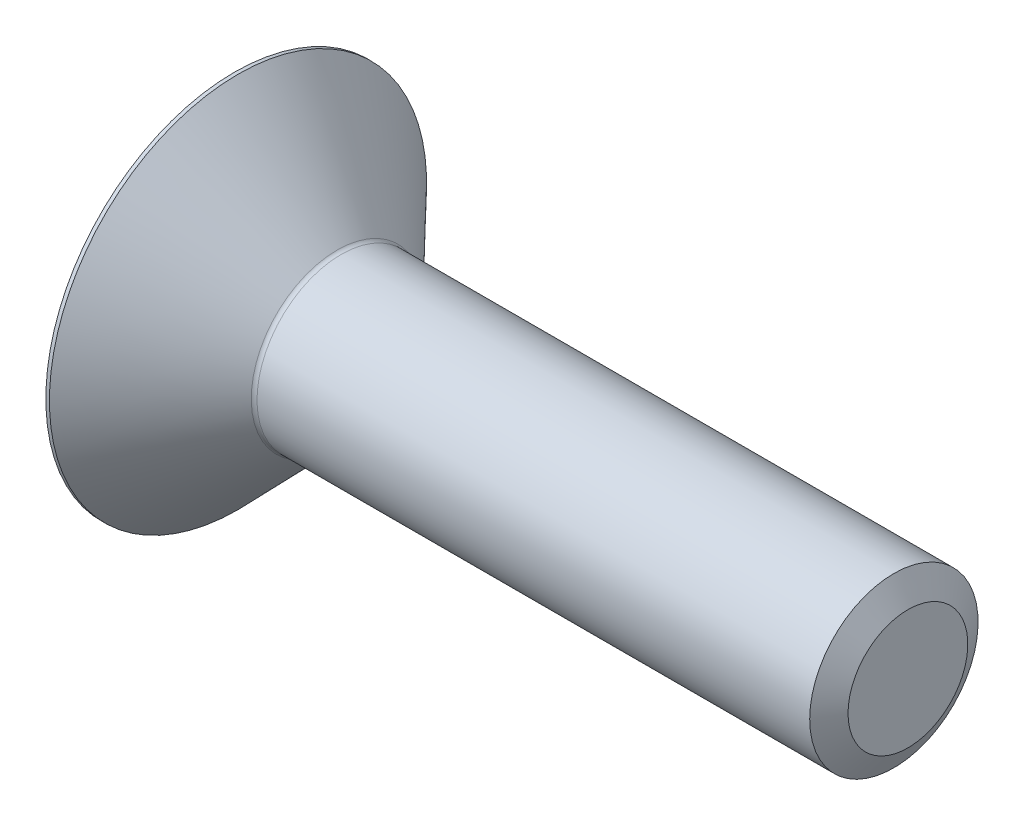
SolidWorks part; units mm, degrees
material "8.8级"
ref_plane "前视基准面" through (0, 0, 0) normal (0, 0, 1) x (1, 0, 0)
ref_plane "上视基准面" through (0, 0, 0) normal (0, 1, 0) x (1, 0, 0)
ref_plane "右视基准面" through (0, 0, 0) normal (1, 0, 0) x (0, 0, -1)
sketch "草图1" plane through (0, 0, 0) normal (0, 0, 1) x (1, 0, 0)
  line L0 (0, 1.5) -> (-10.0976, 1.5)
  line L1 (-10.1695, 1.5305) -> (-11.9362, 3.36)
  line L2 (-11.9362, 3.36) -> (-12, 3.36)
  line L3 (-12, 3.36) -> (-12, 0)
  line L4 (-12, 0) -> (0, 0)
  line L5 (0, 0) -> (0, 1.5)
  line L6 (0, 0) -> (-12, 0) construction
  arc A0 (-10.0976, 1.5) -> (-10.1695, 1.5305) centre (-10.0976, 1.6) cw
  point P9 (-10.14, 1.5)
  dimension "r" = 0.1
  dimension "k" = 1.86
  dimension "dk" = 6.72
  dimension "l" = 12
  dimension "d" = 3
  dimension "D5" = 46
revolve "旋转1" add sketch "草图1" angle 360 about L6
cosmetic thread "装饰螺纹线1" parameters "b"=10, "D2"=2.58
sketch "草图2" plane through (-12, 0, 0) normal (-1, 0, 0) x (0, 0, 1)
  line L1 (0, 1.1547) -> (-1, 0.5774)
  line L2 (-1, 0.5774) -> (-1, -0.5774)
  line L3 (-1, -0.5774) -> (0, -1.1547)
  line L4 (0, -1.1547) -> (1, -0.5774)
  line L5 (1, -0.5774) -> (1, 0.5774)
  line L6 (1, 0.5774) -> (0, 1.1547)
  circle A0 centre (0, 0) radius 1 construction
  dimension "s" = 2
extrude "切除-拉伸1" cut sketch "草图2" against normal blind 1.96
sketch "草图6" plane through (0, 0, 0) normal (0, 0, 1) x (1, 0, 0)
  line L0 (-10.9, 1.1547) -> (-10.2333, 0)
  line L1 (-10.2333, 0) -> (-9.74, 0)
  line L2 (-9.74, 0) -> (-9.74, 1.1547)
  line L3 (-9.74, 1.1547) -> (-10.9, 1.1547)
  line L4 (-12, 0) -> (-10.04, 0) construction
  line L5 (-12, 0) -> (-14.3, 0) construction
  dimension "t" = 1.1
  dimension "D1" = 60
  dimension "t1" = 1.96
  dimension "e-s" = 0.3
  dimension "e" = 2.3
revolve "旋转2" add sketch "草图6" angle 360 about L4
sketch "草图7" plane through (0, 0, 0) normal (0, 0, 1) x (1, 0, 0)
  line L0 (-12, 1.1547) -> (-12, 0)
  line L1 (-12, 0) -> (-11.67, 0)
  line L2 (-11.67, 0) -> (-12, 1.1547)
  line L3 (-12, 0) -> (-11.67, 0) construction
  dimension "e-s*1.1" = 0.33
revolve "切除-旋转2" cut sketch "草图7" angle 360 about L3
sketch "草图4" plane through (0, 0, 0) normal (0, 0, 1) x (1, 0, 0)
  line L0 (-0.25, 1.5) -> (0, 1.067)
  line L1 (0, -1.5) -> (0, 1.5) construction
  line L2 (0, 1.067) -> (0.25, 1.5)
  line L3 (0.25, 1.5) -> (-0.25, 1.5)
  line L4 (-0.25, 0) -> (0.25, 0) construction
  dimension "d" = 3
  dimension "p" = 0.5
revolve "切除-旋转1" cut sketch "草图4" angle 360 about L4
ref_axis "基准轴1" through (-21.1715, 0, 0) along (1, 0, 0)
pattern_linear "阵列(线性)2" [suppressed] count 20 spacing 0.5 along (-1, 0, 0) of bodies 104
equation "\"D2@装饰螺纹线1\" = \"d@草图1\" * 0.86"
equation "\"e-s@草图6\" = \"e@草图6\" - \"s@草图2\""
equation "\"t1@切除-拉伸1\" = \"k@草图1\" + 0.1"
equation "\"t1@草图6\" = \"t1@切除-拉伸1\""
equation "\"e-s*1.1@草图7\" = \"e-s@草图6\" * 1.1"
equation "\"d@草图4\" = \"d@草图1\""
equation "\"D3@阵列(线性)2\" = \"p@草图4\""
equation "\"D1@阵列(线性)2\" = \"b@装饰螺纹线1\" / \"p@草图4\""
